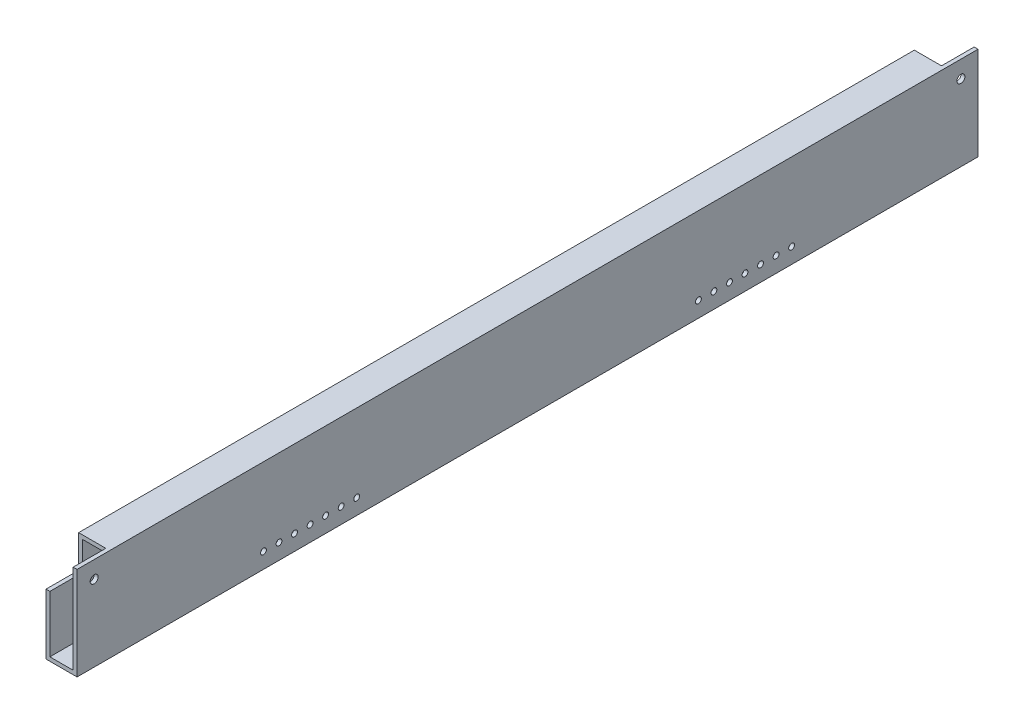
SolidWorks part; units mm, degrees
ref_plane "Front Plane" through (0, 0, 0) normal (0, 0, 1) x (1, 0, 0)
ref_plane "Top Plane" through (0, 0, 0) normal (0, 1, 0) x (1, 0, 0)
ref_plane "Right Plane" through (0, 0, 0) normal (1, 0, 0) x (0, 0, -1)
sketch "Sketch1" plane through (0, 0, 0) normal (0, 0, 1) x (1, 0, 0)
  line L1 (-12.7, -38.1) -> (12.7, -38.1)
  line L2 (-12.7, -38.1) -> (-12.7, 38.1)
  line L3 (-12.7, 38.1) -> (12.7, 38.1)
  line L4 (12.7, -38.1) -> (12.7, 38.1)
  line L5 (-12.7, -38.1) -> (12.7, 38.1) construction
  line L6 (-12.7, 38.1) -> (12.7, -38.1) construction
  point P0 (0, 0)
  dimension "D1" = 25.4
  dimension "D2" = 76.2
extrude "Boss-Extrude1" add sketch "Sketch1" along normal mid plane 736.6
shell "Shell1" thickness 3.175 removed face at (0, 0, -368.3) removed face at (0, 0, 368.3)
sketch "Sketch3" plane through (12.7, 0, 0) normal (1, 0, 0) x (0, 0, -1)
  line L0 (368.3, -38.1) -> (368.3, 38.1) construction
  line L1 (-368.3, -38.1) -> (368.3, -38.1) construction
  line L2 (0, -53.276) -> (0, 47.534) construction
  circle A0 centre (215.9, -25.4) radius 2.3813
  circle A1 centre (203.2, -25.4) radius 2.3813
  circle A2 centre (190.5, -25.4) radius 2.3813
  circle A3 centre (177.8, -25.4) radius 2.3813
  circle A4 centre (165.1, -25.4) radius 2.3813
  circle A5 centre (152.4, -25.4) radius 2.3813
  circle A6 centre (139.7, -25.4) radius 2.3813
  circle A7 centre (-139.7, -25.4) radius 2.3813
  circle A8 centre (-152.4, -25.4) radius 2.3813
  circle A9 centre (-165.1, -25.4) radius 2.3813
  circle A10 centre (-203.2, -25.4) radius 2.3813
  circle A11 centre (-177.8, -25.4) radius 2.3813
  circle A12 centre (-215.9, -25.4) radius 2.3813
  circle A13 centre (-190.5, -25.4) radius 2.3813
  dimension "D1" = 4.7625
  dimension "D3" = 12.7
  dimension "D4" = 12.7
  dimension "D5" = 12.7
  dimension "D6" = 12.7
  dimension "D7" = 12.7
  dimension "D8" = 12.7
  dimension "D9" = 12.7
  dimension "D10" = 12.7
  dimension "D2" = 152.4
extrude "Cut-Extrude2" cut sketch "Sketch3" against normal up to next
sketch "Sketch4" plane through (-12.7, 0, 0) normal (-1, 0, 0) x (0, 0, 1)
  line L1 (-368.3, 38.1) -> (-341.63, 38.1)
  line L2 (-368.3, 38.1) -> (-368.3, 11.43)
  line L3 (-368.3, 11.43) -> (-341.63, 11.43)
  line L4 (-341.63, 38.1) -> (-341.63, 11.43)
  line L5 (368.3, 38.1) -> (341.63, 38.1)
  line L6 (368.3, 38.1) -> (368.3, 11.43)
  line L7 (368.3, 11.43) -> (341.63, 11.43)
  line L8 (341.63, 38.1) -> (341.63, 11.43)
  dimension "D1" = 26.67
  dimension "D2" = 26.67
  dimension "D3" = 26.67
  dimension "D4" = 26.67
extrude "Cut-Extrude3" cut sketch "Sketch4" against normal blind 22.225
sketch "Sketch5" plane through (9.525, 0, 0) normal (-1, 0, 0) x (0, 0, 1)
  line L0 (-341.63, 38.1) -> (-368.3, 38.1) construction
  line L1 (-368.3, -34.925) -> (-368.3, 38.1) construction
  line L2 (368.3, 38.1) -> (341.63, 38.1) construction
  line L4 (368.3, -34.925) -> (368.3, 38.1) construction
  circle A0 centre (-354.33, 24.13) radius 3.25
  circle A1 centre (354.33, 24.13) radius 3.25
  dimension "D3" = 6.5
  dimension "D4" = 6.5
  dimension "D6" = 13.97
  dimension "D1" = 13.97
  dimension "D2" = 13.97
  dimension "D5" = 13.97
extrude "Cut-Extrude4" cut sketch "Sketch5" against normal blind 22.225
equation "\"robotwidth\"= 29in"
equation "\"D1@Boss-Extrude1\"=\"robotwidth\""
